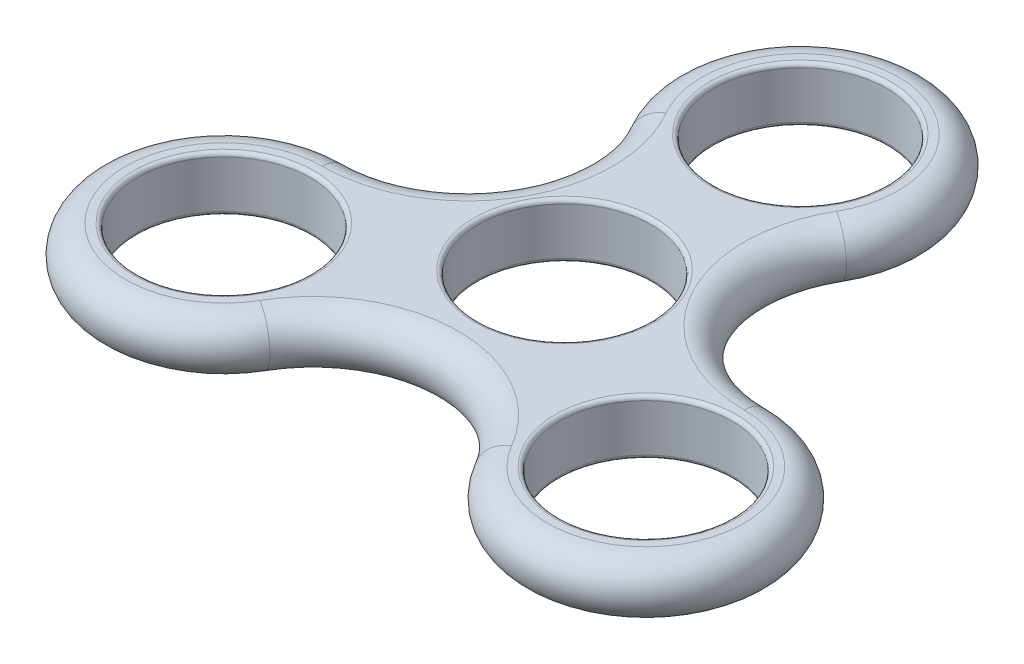
SolidWorks part; units mm, degrees
ref_plane "Front Plane" through (0, 0, 0) normal (0, 0, 1) x (1, 0, 0)
ref_plane "Top Plane" through (0, 0, 0) normal (0, 1, 0) x (1, 0, 0)
ref_plane "Right Plane" through (0, 0, 0) normal (1, 0, 0) x (0, 0, -1)
sketch "Sketch1" plane through (0, 0, 0) normal (0, 1, 0) x (1, 0, 0)
  line L0 (0, 30) -> (0, 0) construction
  circle A0 centre (0, 0) radius 11
  circle A1 centre (0, 30) radius 11
  circle A2 centre (26.8468, -16.5) radius 11
  circle A3 centre (-26.8468, -16.5) radius 11
  circle A4 centre (-26.8468, -16.5) radius 16
  circle A5 centre (0, 30) radius 16
  circle A6 centre (26.8468, -16.5) radius 16
  arc A7 (-12.9904, -24.5) -> (12.9904, -24.5) centre (0, -32) cw
  arc A8 (-13.8564, 22) -> (-26.8468, -0.5) centre (-26.8468, 14.5) cw
  arc A9 (26.8468, -0.5) -> (13.8564, 22) centre (26.8468, 14.5) cw
  point P11 (0, -1)
  point P27 (0, 0)
  point P28 (0, 0)
  dimension "D1" = 22
  dimension "D5" = 15
  dimension "D6" = 15
  dimension "D7" = 15
  dimension "D8" = 5
  dimension "D2" = 30
  dimension "D4" = 5
  dimension "D3" = 3
extrude "Boss-Extrude1" add sketch "Sketch1" along normal mid plane 7 contours A4 A3 | A1 A5 | A6 A2 | A6 A9 A5 A0 A8 A4 A7 region at (-11.8291, 0, 20.524) region at (-15.0308, 0, 4.684) region at (-4.024, 0, -45.0177) region at (13.3823, 0, 8.7263)
fillet "Fillet1" 2 edges at (40.7032, 3.5, 24.5) (40.7032, -3.5, 24.5) type full round first side face at (-26.8468, 3.5, 27.5) second side face at (-26.8468, -3.5, 27.5) middle face at (30.3109, 0, 18.5)
fillet "Fillet2" radius 0.5 8 edges at (-26.8468, -3.5, 27.5) (-26.8468, 3.5, 27.5) (26.8468, -3.5, 27.5) (26.8468, 3.5, 27.5) (0, -3.5, 11) (0, 3.5, 11) (0, -3.5, -19) (0, 3.5, -19)
